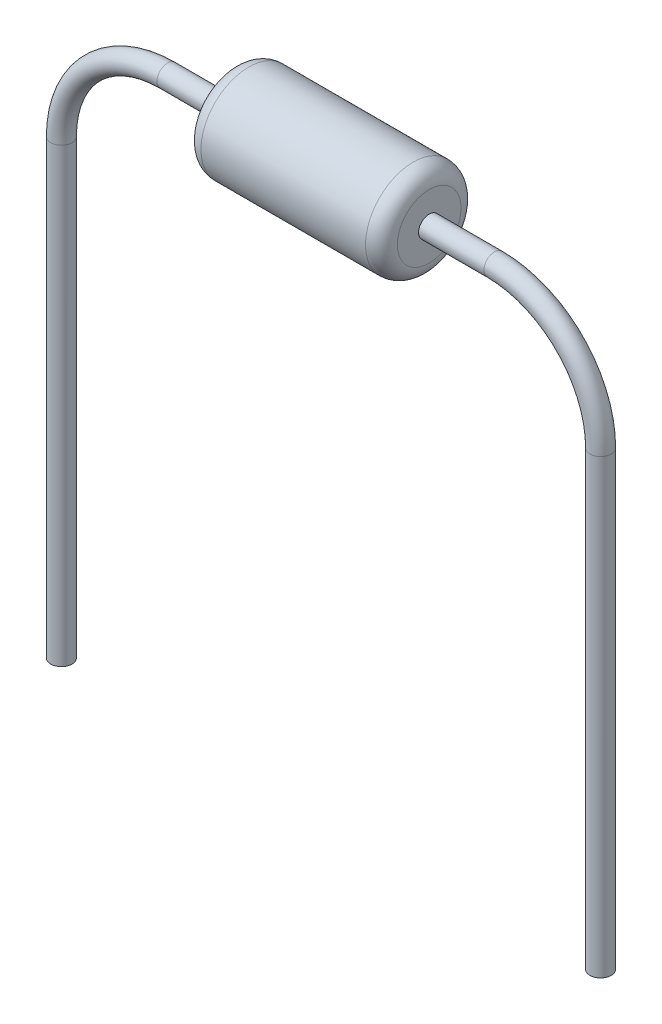
SolidWorks part; units mm, degrees
other "Cathode Band"
other "Wire"
other "Diode"
other "Center"
material "Glass"
ref_plane "Front Plane" through (0, 0, 0) normal (0, 0, 1) x (1, 0, 0)
ref_plane "Top Plane" through (0, 0, 0) normal (0, 1, 0) x (1, 0, 0)
ref_plane "Right Plane" through (0, 0, 0) normal (1, 0, 0) x (0, 0, -1)
sketch "Sketch1" plane through (0, 0, 0) normal (1, 0, 0) x (0, 0, -1)
  circle A0 centre (0, 0) radius 0.2
  circle A1 centre (0, 0) radius 0.4
  dimension "D1" = 0.8
  dimension "D2" = 0.4
extrude "Boss-Extrude1" add sketch "Sketch1" along normal mid plane 3.5
fillet "Fillet2" radius 0.1 2 edges at (-1.75, 0, -0.4) (1.75, 0, -0.4)
sketch "Sketch4" plane through (0, 0, 0) normal (1, 0, 0) x (0, 0, -1)
  circle A0 centre (0, 0) radius 0.2 construction
  circle A1 centre (0, 0) radius 0.2
  circle A2 centre (0, 0) radius 0.9
  dimension "D1" = 1.8
extrude "Boss-Extrude2" add sketch "Sketch4" along normal mid plane 3.7 separate body
fillet "Fillet1" radius 0.3 2 edges at (-1.85, 0, -0.9) (1.85, 0, -0.9)
sketch "Sketch6" plane through (0, 0, 0) normal (0, 0, 1) x (1, 0, 0)
  line L0 (0, 0) -> (-3.08, 0)
  line L1 (-5.08, -2) -> (-5.08, -10.5082)
  line L2 (5.08, -2) -> (5.08, -10.5082)
  line L3 (-5.08, -10.5082) -> (5.08, -10.5082) construction
  line L4 (0, 0) -> (0, -10.5082) construction
  line L5 (0, 0) -> (3.08, 0)
  arc A0 (-3.08, 0) -> (-5.08, -2) centre (-3.08, -2) ccw
  arc A1 (3.08, 0) -> (5.08, -2) centre (3.08, -2) cw
  dimension "D2" = 2
  dimension "D1" = 10.16
sketch "Sketch7" plane through (0, 0, 0) normal (1, 0, 0) x (0, 0, -1)
  circle A0 centre (0, 0) radius 0.2
  dimension "D1" = 0.4
sweep "Sweep1" add profiles "Sketch7" path "Sketch6"
sketch "Sketch8" plane through (0, 0, 0) normal (0, 0, 1) x (1, 0, 0)
  line L0 (0, 0) -> (-0.95, 0) construction
  line L1 (-1.65, 0.4) -> (-1.65, -0.4) construction
  line L2 (-0.95, 0) -> (-1.65, 0) construction
  line L3 (-0.95, 0.42) -> (-0.95, 0.75)
  line L4 (-1, 0.8) -> (-1.55, 0.8)
  line L5 (-1.65, 0.42) -> (-1.65, 0.7)
  line L6 (-1.65, 0.42) -> (-0.95, 0.42)
  line L7 (-1.65, 0.42) -> (-1.65, 0) construction
  line L8 (-0.95, 0.42) -> (-0.95, 0) construction
  arc A0 (-1.55, 0.8) -> (-1.65, 0.7) centre (-1.55, 0.7) ccw
  arc A1 (-0.95, 0.75) -> (-1, 0.8) centre (-1, 0.75) ccw
  dimension "D4" = 0.1
  dimension "D5" = 0.05
  dimension "D1" = 0.8
  dimension "D2" = 0.7
  dimension "D3" = 0.42
revolve "Revolve2" add sketch "Sketch8" angle 360 about L2
sketch "Sketch9" plane through (0, 0, 0) normal (0, 0, 1) x (1, 0, 0)
  line L0 (0, 0) -> (0, 0.4) construction
  line L1 (1.65, 0.4) -> (-1.65, 0.4) construction
  line L2 (-1.65, 0) -> (1.65, 0) construction
  line L3 (1.65, -0.4) -> (1.65, 0.4) construction
  circle A0 centre (0, 0.4) radius 0.05
  dimension "D1" = 0.1
revolve "Cut-Revolve1" cut sketch "Sketch9" angle 360 about L2
fillet "Fillet3" radius 0.1 2 edges at (0.05, 0, 0.4) (-0.05, 0, -0.4)
